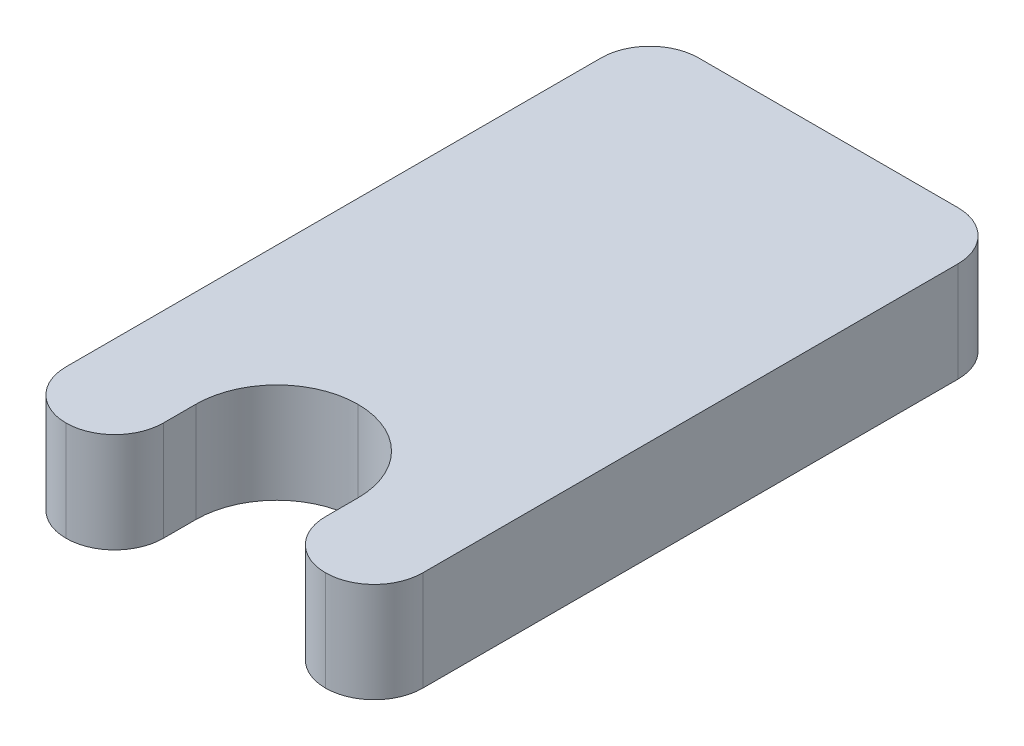
SolidWorks part; units mm, degrees
ref_plane "Front" through (0, 0, 0) normal (0, 0, 1) x (1, 0, 0)
ref_plane "Top" through (0, 0, 0) normal (0, 1, 0) x (1, 0, 0)
ref_plane "Right" through (0, 0, 0) normal (1, 0, 0) x (0, 0, -1)
sketch "Sketch1" plane through (0, 0, 0) normal (0, 1, 0) x (1, 0, 0)
  line L1 (-15.5, -15.5) -> (15.5, -15.5) construction
  line L2 (-15.5, -15.5) -> (-15.5, 15.5) construction
  line L3 (-15.5, 15.5) -> (15.5, 15.5) construction
  line L4 (15.5, -15.5) -> (15.5, 15.5) construction
  line L5 (-15.5, -15.5) -> (15.5, 15.5) construction
  line L6 (-15.5, 15.5) -> (15.5, -15.5) construction
  line L7 (-21, -21) -> (21, -21)
  line L8 (-21, -21) -> (-21, 21)
  line L9 (-21, 21) -> (21, 21)
  line L10 (21, -21) -> (21, 21)
  line L11 (-21, -21) -> (21, 21) construction
  line L12 (-21, 21) -> (21, -21) construction
  circle A0 centre (0, 0) radius 2.5
  circle A1 centre (-15.5, 15.5) radius 1.6
  circle A2 centre (15.5, 15.5) radius 1.6
  circle A3 centre (15.5, -15.5) radius 1.6
  circle A4 centre (-15.5, -15.5) radius 1.6
  circle A5 centre (0, 0) radius 11
  dimension "D1" = 5
  dimension "D3" = 3.2
  dimension "D5" = 22
  dimension "D2" = 31
  dimension "D4" = 42
sketch "Sketch2" plane through (0, 0, 0) normal (0, 1, 0) x (1, 0, 0)
  line L0 (-2.5, 2.5) -> (-2.5, -2.5)
  line L3 (2.5, 2.5) -> (-2.5, 2.5)
  line L7 (-15.5, -15.5) -> (15.5, 15.5) construction
  line L8 (-2.5, -2.5) -> (-5.5, -2.5)
  line L9 (-5.5, -2.5) -> (-5.5, 17)
  line L10 (-5.5, 17) -> (5.5, 17)
  line L11 (0, 0) -> (0, 2.5) construction
  line L12 (5.5, -2.5) -> (5.5, 17)
  line L13 (2.5, -2.5) -> (5.5, -2.5)
  line L14 (2.5, 2.5) -> (2.5, -2.5)
  circle A0 centre (0, 0) radius 2.5 construction
  circle A1 centre (0, 0) radius 11 construction
  point P19 (0, 11)
  dimension "D1" = 3
  dimension "D2" = 6
extrude "Boss-Extrude1" add sketch "Sketch2" along normal blind 3.08
fillet "Fillet1" radius 2.5 2 edges at (-2.5, 1.54, -2.5) (2.5, 1.54, -2.5)
fillet "Fillet2" radius 1.5 6 edges at (-5.5, 1.54, -17) (5.5, 1.54, -17) (5.5, 1.54, 2.5) (2.5, 1.54, 2.5) (-5.5, 1.54, 2.5) (-2.5, 1.54, 2.5)
